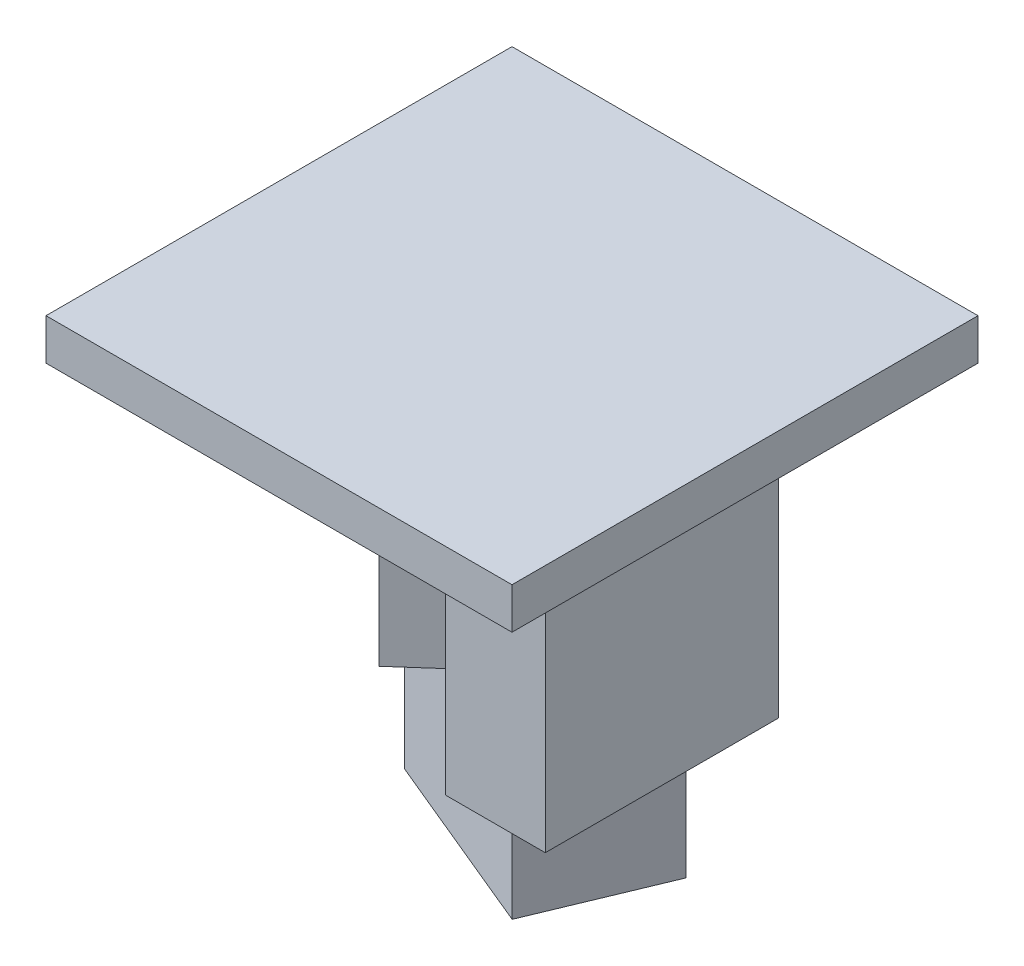
SolidWorks part; units mm, degrees
ref_plane "Front Plane" through (0, 0, 0) normal (0, 0, 1) x (1, 0, 0)
ref_plane "Top Plane" through (0, 0, 0) normal (0, 1, 0) x (1, 0, 0)
ref_plane "Right Plane" through (0, 0, 0) normal (1, 0, 0) x (0, 0, -1)
sketch "Sketch2" plane through (0, 0, 0) normal (0, 1, 0) x (1, 0, 0)
  line L1 (-88.9, 88.9) -> (88.9, 88.9)
  line L2 (-88.9, 88.9) -> (-88.9, -88.9)
  line L3 (-88.9, -88.9) -> (88.9, -88.9)
  line L4 (88.9, 88.9) -> (88.9, -88.9)
  dimension "D1" = 177.8
  dimension "D2" = 177.8
  dimension "D3" = 88.9
  dimension "D4" = 88.9
extrude "Boss-Extrude2" add sketch "Sketch2" along normal blind 12.7
extrude "Boss-Extrude3" add sketch "Sketch2<2>" against normal blind 3
sketch "Sketch2<2>" plane through (0, 0, 0) normal (0, 1, 0) x (1, 0, 0) same geometry as "Sketch2"
sketch "Sketch3" plane through (0, -3, 0) normal (0, -1, 0) x (1, 0, 0)
  line L0 (-25.4753, -50.8) -> (-63.5, -17.1137)
  line L1 (-63.5, -17.1137) -> (-29.8137, 20.9109)
  line L2 (-29.8137, 20.9109) -> (8.2109, -12.7753)
  line L3 (8.2109, -12.7753) -> (-25.4753, -50.8)
  line L4 (88.9, -88.9) -> (-88.9, -88.9) construction
  line L5 (-88.9, -88.9) -> (-88.9, 88.9) construction
  line L6 (88.9, 88.9) -> (88.9, -88.9) construction
  line L7 (63.5, -38.1) -> (25.4, -38.1)
  line L8 (63.5, -38.1) -> (63.5, 50.8)
  line L9 (63.5, 50.8) -> (25.4, 50.8)
  line L10 (25.4, -38.1) -> (25.4, 50.8)
  dimension "D1" = 50.8
  dimension "D2" = 50.8
  dimension "D3" = 38.1
  dimension "D4" = 25.4
  dimension "D5" = 38.1
  dimension "D6" = 88.9
  dimension "D7" = 50.8
  dimension "D8" = 25.4
extrude "Boss-Extrude4" add sketch "Sketch3" along normal blind 104.6
sketch "Sketch4" plane through (0, -107.6, 0) normal (0, -1, 0) x (1, 0, 0)
  line L0 (-25.4753, -50.8) -> (44.8921, -21.5619)
  line L1 (44.8921, -21.5619) -> (25.4, 25.3497)
  line L2 (25.4, 50.8) -> (25.4, -38.1) construction
  line L3 (25.4, 25.3497) -> (-44.9674, -3.8884)
  line L4 (-44.9674, -3.8884) -> (-25.4753, -50.8)
  dimension "D1" = 76.2
  dimension "D2" = 50.8
extrude "Boss-Extrude5" add sketch "Sketch4" along normal blind 53.8
